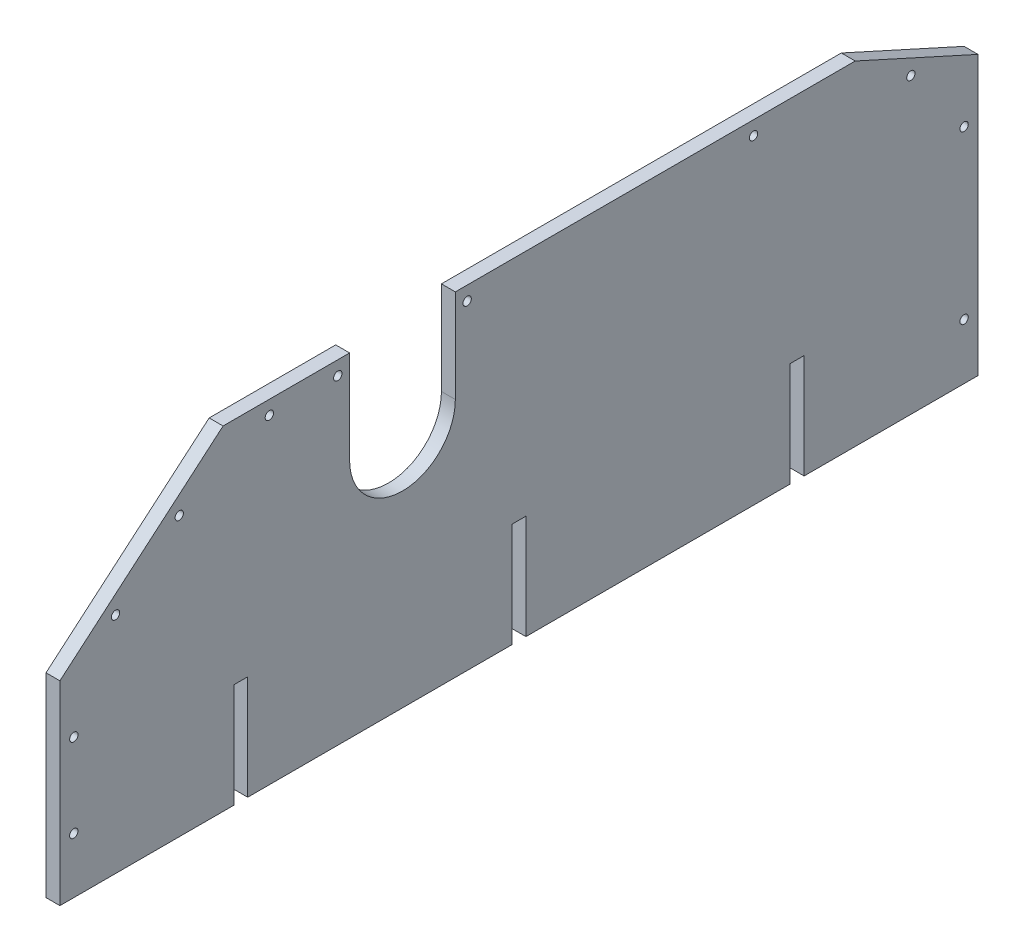
SolidWorks part; units mm, degrees
material "PMMA"
ref_plane "Front Plane" through (0, 0, 0) normal (0, 0, 1) x (1, 0, 0)
ref_plane "Top Plane" through (0, 0, 0) normal (0, 1, 0) x (1, 0, 0)
ref_plane "Right Plane" through (0, 0, 0) normal (1, 0, 0) x (0, 0, -1)
sketch "Schizzo1" plane through (0, 0, 0) normal (1, 0, 0) x (0, 0, -1)
  line L0 (165, 60) -> (-165, -60) construction
  line L1 (165, 60) -> (-106.354, 60)
  line L2 (-106.354, 60) -> (-165, 10)
  line L3 (-165, -60) -> (165, -60)
  line L4 (165, 60) -> (165, -60)
  line L5 (-165, 10) -> (-165, -60)
  point P0 (0, 0)
  dimension "D1" = 120
  dimension "D2" = 330
  dimension "D3" = 50
  dimension "D4" = 40.45
extrude "Estrusione-Estrusione1" add sketch "Schizzo1" along normal blind 5
sketch "Schizzo7" plane through (0, 0, 0) normal (1, 0, 0) x (0, 0, -1)
  line L0 (165, 40) -> (165, 60)
  line L1 (165, -60) -> (165, 60) construction
  line L2 (165, 60) -> (120.8693, 60)
  line L3 (165, 60) -> (-106.354, 60) construction
  line L4 (120.8693, 60) -> (165, 40)
  line L5 (-106.354, 60) -> (-106.354, -60) construction
  line L6 (-165, -60) -> (165, -60) construction
  line L7 (-165, -60) -> (165, -60) construction
  line L8 (-106.354, 60) -> (-165, 10) construction
  line L9 (-165, 10) -> (-165, -60) construction
  dimension "D1" = 100
  dimension "D2" = 24.38
  dimension "D3" = 49.55
  dimension "D4" = 65.62
  dimension "D5" = 155.62
extrude "Taglio-Estrusione5" cut sketch "Schizzo7" along direction (1, 0, 0) on the side of the normal through all
sketch "Schizzo2" plane through (5, 0, 0) normal (1, 0, 0) x (0, 0, -1)
  line L0 (0, -60) -> (0, 60) construction
  line L1 (-165, -60) -> (165, -60) construction
  line L3 (102.5, -60) -> (102.5, -22.5)
  line L4 (2.5, -60) -> (-2.5, -60)
  line L5 (2.5, -60) -> (2.5, -22.5)
  line L6 (2.5, -22.5) -> (-2.5, -22.5)
  line L7 (-2.5, -60) -> (-2.5, -22.5)
  line L8 (102.5, -22.5) -> (97.5, -22.5)
  line L9 (97.5, -60) -> (97.5, -22.5)
  line L10 (102.5, -60) -> (97.5, -60)
  line L11 (-97.5, -60) -> (-97.5, -22.5)
  line L12 (-97.5, -22.5) -> (-102.5, -22.5)
  line L13 (-102.5, -60) -> (-102.5, -22.5)
  line L14 (-97.5, -60) -> (-102.5, -60)
  point P10 (0, -22.5)
  dimension "D2" = 37.5
  dimension "D4" = 2
extrude "Taglio-Estrusione1" cut sketch "Schizzo2" along direction (1, 0, 0) on the side against the normal through all from surface starting at face at (5, 8.3333, -2.4192)
sketch "Schizzo3" plane through (0, 0, 0) normal (1, 0, 0) x (0, 0, -1)
  line L0 (-165, 10) -> (-165, -60) construction
  line L1 (-41.87, 26.5) -> (-41.87, 60) construction
  line L2 (-106.354, 60) -> (-165, 10) construction
  line L3 (-122.1057, 40) -> (-166.5246, 2.1297) construction
  line L4 (-41.87, 26.5) -> (-41.87, 60) construction
  line L5 (-60.87, 26.5) -> (-60.87, 60)
  line L6 (-22.87, 26.5) -> (-22.87, 60)
  line L7 (-165, -60) -> (-102.5, -60) construction
  line L8 (120.8693, 60) -> (-106.354, 60) construction
  line L9 (-160, -12.0193) -> (-160, -60) construction
  line L10 (-89.7177, 55) -> (290.1704, 55) construction
  line L11 (160, -60) -> (160, 42.266) construction
  line L12 (102.5, -60) -> (165, -60) construction
  line L13 (120.8693, 60) -> (165, 40) construction
  line L14 (165, -60) -> (165, 40) construction
  line L15 (108.7565, 60) -> (165, 34.5105) construction
  line L16 (120.8693, 60) -> (-106.354, 60) construction
  line L17 (150.7275, 67.1952) -> (135.1418, 32.8048) construction
  line L18 (165, -60) -> (165, 40) construction
  line L19 (165, -10) -> (125.4187, -10) construction
  line L20 (-165, 10) -> (-165, -60) construction
  line L21 (-165, -25) -> (-129.0202, -25) construction
  circle A0 centre (-65.12, 55) radius 1.5
  arc A1 (-60.87, 26.5) -> (-22.87, 26.5) centre (-41.87, 26.5) ccw
  arc A2 (-22.87, 60) -> (-60.87, 60) centre (-41.87, 60) ccw
  circle A3 centre (-18.62, 55) radius 1.5
  circle A4 centre (-89.7177, 55) radius 1.5
  circle A5 centre (84.3101, 55) radius 1.5
  circle A6 centre (187.2402, 55) radius 1.5
  circle A7 centre (290.1704, 55) radius 1.5
  circle A8 centre (-122.1057, 40) radius 1.5
  circle A9 centre (-145, 20.4809) radius 1.5
  circle A10 centre (-160, -10) radius 1.5
  circle A11 centre (-160, -40) radius 1.5
  circle A12 centre (160, -40) radius 1.5
  circle A14 centre (160, 20) radius 1.5
  circle A15 centre (140.8707, 45.4459) radius 1.5
  point P10 (-41.87, 43.25)
  point P63 (142.9347, 50)
  dimension "D3" = 19
  dimension "D4" = 3
  dimension "D6" = 5
  dimension "D1" = 123.13
  dimension "D2" = 23.25
  dimension "D8" = 5
  dimension "D9" = 20
  dimension "D11" = 20
  dimension "D12" = 5
  dimension "D13" = 20
  dimension "D15" = 20
  dimension "D16" = 5
  dimension "D17" = 5
  dimension "D20" = 27.9807
  dimension "D22" = 5
  dimension "D14" = 20
  dimension "D5" = 2
  dimension "D7" = 4
  dimension "D10" = 2
extrude "Taglio-Estrusione2" cut sketch "Schizzo3" along direction (1, 0, 0) on the side of the normal through all
equation "\"Thickness5\"= 5"
equation "\"D1@Estrusione-Estrusione1\"=\"Thickness5\""
equation "\"D1@Schizzo2\"=\"Thickness5\""
equation "\"D11@Schizzo3\"=\"D9@Schizzo3\""
